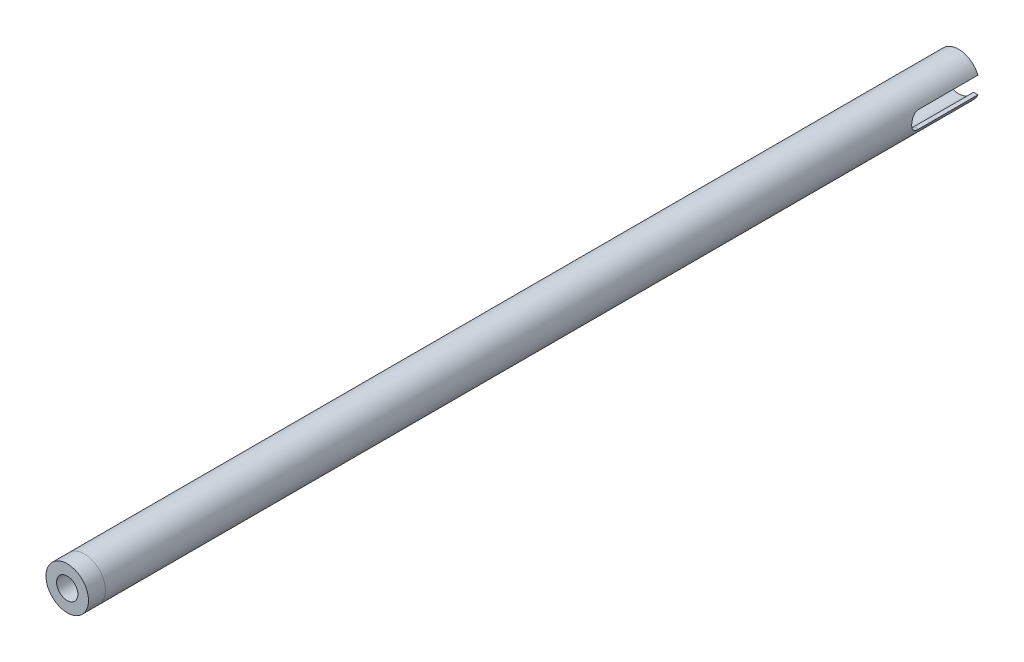
SolidWorks part; units mm, degrees
material "AISI 4130 Steel, normalized at 870C"
ref_plane "Front Plane" through (0, 0, 0) normal (0, 0, 1) x (1, 0, 0)
ref_plane "Top Plane" through (0, 0, 0) normal (0, 1, 0) x (1, 0, 0)
ref_plane "Right Plane" through (0, 0, 0) normal (1, 0, 0) x (0, 0, -1)
sketch "Axis" plane through (0, 0, 0) normal (0, 1, 0) x (1, 0, 0)
  line L0 (0, 0) -> (0, 332.6618) construction
  line L1 (0, 0) -> (0, -28.575) construction
  line L2 (0, 332.6618) -> (-7.9375, 332.6618) construction
  line L3 (0, 361.4136) -> (-10.3187, 324.0363) construction
  dimension "D1" = 28.575
  dimension "D2" = 7.9375
sketch "Sketch1" plane through (0, 0, 0) normal (0, 0, 1) x (1, 0, 0)
  line L0 (-7.9375, 0) -> (7.9375, 0) construction
  line L1 (-7.2748, 3.175) -> (7.2748, 3.175)
  line L2 (-7.2748, -3.175) -> (7.2748, -3.175)
  circle A0 centre (0, 0) radius 7.9375
  circle A1 centre (0, 0) radius 6.4643
  circle A2 centre (0, 0) radius 3.9688
  dimension "D1" = 15.875
  dimension "D3" = 7.9375
  dimension "D2" = 1.4732
  dimension "D4" = 6.35
extrude "Threaded insert 1-1" add sketch "Sketch1" against normal blind 6.35 contours A2 L1 A1 | A1 L1 A0 | A2 L0 A1 L1 | A1 L0 A0 L1 | L0 A1 L2 A0 | L0 A2 L2 A1 | A2 L2 A1 | A1 L2 A0 | L0 A1 L2 A2 | L0 A0 L2 A1 | A0 L0 A1 L1 | A1 L0 A2 L1 region at (4.8156, 1.6537, 0) region at (4.8156, -1.6537, 0) region at (6.9501, 1.6161, 0) region at (6.9501, -1.6161, 0) region at (-4.8156, -1.6537, 0) region at (-4.8156, 1.6537, 0) region at (0, 4.6361, 0) region at (0, -4.6361, 0) region at (0, 6.6174, 0) region at (6.4528, -3.3281, 0) region at (-6.9501, -1.6161, 0) region at (-6.9501, 1.6161, 0)
extrude "Threaded insert 1-2" add sketch "Sketch1<3>" against normal blind 9.525 from surface contours A2 L1 A1 | A2 L0 A1 L1 | L0 A2 L2 A1 | A2 L2 A1 | L0 A1 L2 A2 | A1 L0 A2 L1 region at (4.8156, 1.6537, 0) region at (4.8156, -1.6537, 0) region at (-4.8156, -1.6537, 0) region at (-4.8156, 1.6537, 0) region at (0, 4.6361, 0) region at (0, -4.6361, 0) starting at face at (7.9375, 0, -6.35)
sketch "Sketch1<3>" plane through (0, 0, 0) normal (0, 0, 1) x (1, 0, 0) same geometry as "Sketch1"
extrude "A-arm tube" add sketch "Sketch1<4>" against normal up to vertex (332.6618 mm away) from surface separate body contours A1 L1 A0 | A1 L0 A0 L1 | L0 A1 L2 A0 | A1 L2 A0 | L0 A0 L2 A1 | A0 L0 A1 L1 region at (6.9501, 1.6161, 0) region at (6.9501, -1.6161, 0) region at (0, 6.6174, 0) region at (6.4528, -3.3281, 0) region at (-6.9501, -1.6161, 0) region at (-6.9501, 1.6161, 0) up to point (0, 0, -332.6618) starting at face at (6.4643, 0, -6.35)
sketch "Sketch1<4>" plane through (0, 0, 0) normal (0, 0, 1) x (1, 0, 0) same geometry as "Sketch1"
extrude "Apex slot" cut sketch "Sketch1<5>" along normal blind 25.4 from surface contours A0 L0 A1 L1 | L0 A0 L2 A1 | A1 L0 A0 L1 | L0 A1 L2 A0 region at (6.9501, 1.6161, 0) region at (6.9501, -1.6161, 0) region at (-6.9501, -1.6161, 0) region at (-6.9501, 1.6161, 0) starting at face at (6.4643, 0, -332.6618)
sketch "Sketch1<5>" plane through (0, 0, 0) normal (0, 0, 1) x (1, 0, 0) same geometry as "Sketch1"
fillet "Fillet1" radius 3.175 4 edges at (-6.4528, 3.175, -307.2618) (-6.4528, -3.175, -307.2618) (6.4528, -3.175, -307.2618) (6.4528, 3.175, -307.2618)
equation "\"tube diameter\"= 5 / 8"
equation "\"tube thickness\"= .058"
equation "\"apex thickness\"= .25"
equation "\"tube slot\"= 1"
equation "\"D1@Sketch1\"=\"tube diameter\""
equation "\"D2@Sketch1\"=\"tube thickness\""
equation "\"threaded insert hole\"= .3125"
equation "\"D3@Sketch1\"=\"threaded insert hole\""
equation "\"D4@Sketch1\"=\"apex thickness\""
equation "\"D1@Apex slot\" = \"tube slot\""
equation "\"D1@Fillet1\"=\"apex thickness\"/2"
equation "\"D2@Axis\"=\"tube diameter\"/2"
